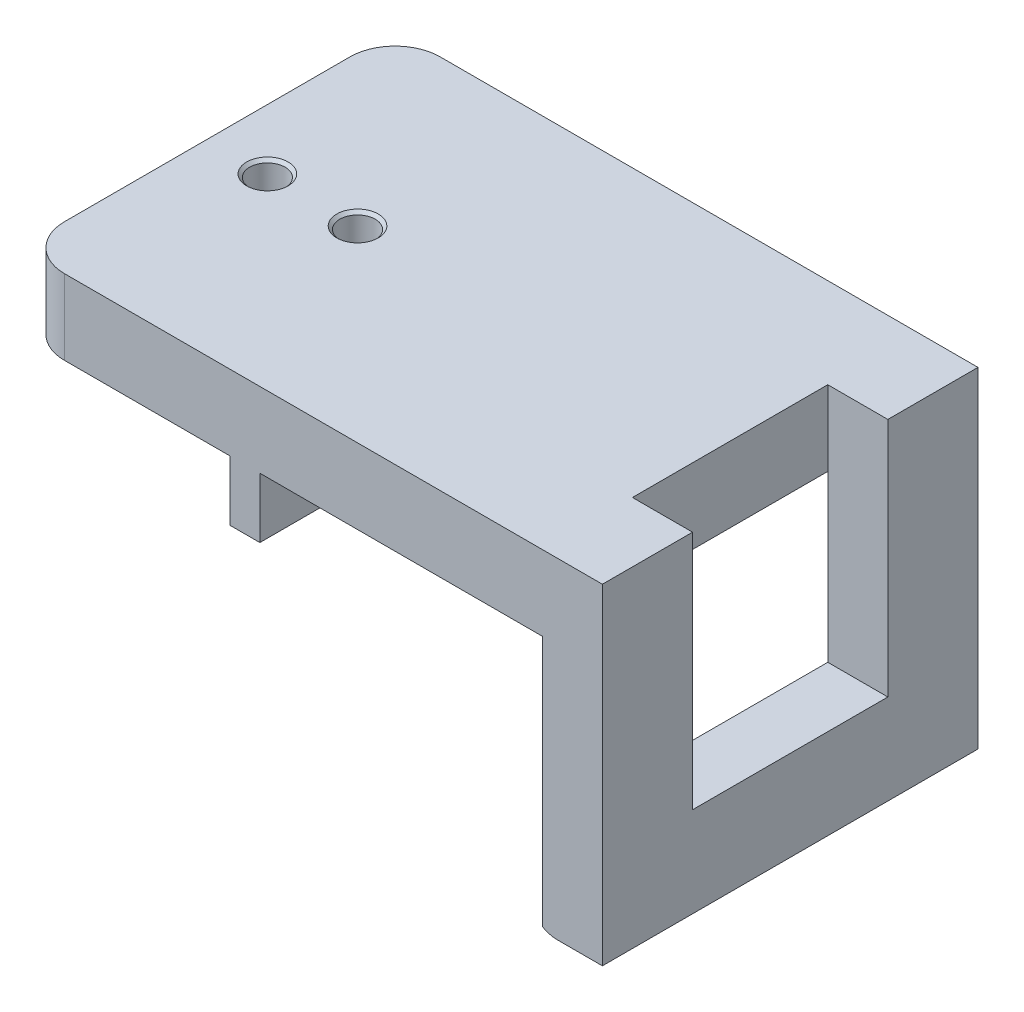
SolidWorks part; units mm, degrees
ref_plane "Front Plane" through (0, 0, 0) normal (0, 0, 1) x (1, 0, 0)
ref_plane "Top Plane" through (0, 0, 0) normal (0, 1, 0) x (1, 0, 0)
ref_plane "Right Plane" through (0, 0, 0) normal (1, 0, 0) x (0, 0, -1)
sketch "Sketch1" plane through (0, 0, 0) normal (0, 1, 0) x (1, 0, 0)
  line L1 (0, 0) -> (44.196, 0)
  line L2 (0, 0) -> (0, 31.75)
  line L3 (0, 31.75) -> (44.196, 31.75)
  line L4 (44.196, 0) -> (44.196, 31.75)
  dimension "D1" = 44.196
  dimension "D2" = 31.75
extrude "Boss-Extrude1" add sketch "Sketch1" along normal blind 6.35
sketch "Sketch3" plane through (0, 0, 0) normal (0, -1, 0) x (1, 0, 0)
  line L0 (44.196, -31.75) -> (0, -31.75) construction
  line L1 (20.32, 0) -> (17.78, 0)
  line L2 (20.32, 0) -> (20.32, -31.75)
  line L3 (20.32, -31.75) -> (17.78, -31.75)
  line L4 (17.78, 0) -> (17.78, -31.75)
  line L6 (44.196, 0) -> (44.196, -31.75) construction
  dimension "D1" = 2.54
  dimension "D2" = 23.876
extrude "Boss-Extrude3" add sketch "Sketch3" along normal blind 5.08
hole_wizard "Ø3.0mm Dowel Hole1" positions "Sketch5" profile "Sketch4" hole size "Ø3.0" standard "ISO" end condition through all
sketch "Sketch5" plane through (0, 6.35, 0) normal (0, 1, 0) x (1, 0, 0)
  line L0 (0, 0) -> (44.196, 0) construction
  line L1 (0, 31.75) -> (0, 0) construction
  point P0 (5.08, 15.875)
  point P2 (12.7, 15.875)
  dimension "D1" = 15.875
  dimension "D2" = 5.08
  dimension "D3" = 7.62
sketch "Sketch4" plane through (5.08, 6.35, -15.875) normal (1, 0, 0) x (0, 0, 1)
  line L0 (0, 0) -> (0, 11.43)
  line L1 (0, 11.43) -> (1.5, 11.43)
  line L2 (1.5, 11.43) -> (1.5, 0)
  line L5 (1.5, 0) -> (0, 0)
  line L11 (0, -6.35) -> (0, 107.95) construction
  dimension "Thru Hole Dia." = 3
  dimension "Thru Hole Depth" = 11.43
chamfer "Chamfer1" distance 0.254 angle 45 4 edges at (12.7, 6.35, -14.375) (5.08, 6.35, -14.375) (5.08, 0, -17.375) (12.7, 0, -17.375)
fillet "Fillet2" radius 3.81 2 edges at (0, 3.175, 0) (0, 3.175, -31.75)
sketch "Sketch6" plane through (44.196, 0, 0) normal (1, 0, 0) x (0, 0, -1)
  line L0 (0, 6.35) -> (0, -21.59)
  line L1 (31.75, 6.35) -> (31.75, -21.59)
  line L2 (31.75, -21.59) -> (0, -21.59)
  line L3 (0, 6.35) -> (7.62, 6.35)
  line L4 (0, 6.35) -> (31.75, 6.35) construction
  line L5 (7.62, 6.35) -> (7.62, -13.97)
  line L6 (7.62, -13.97) -> (24.13, -13.97)
  line L7 (24.13, -13.97) -> (24.13, 6.35)
  line L8 (24.13, 6.35) -> (31.75, 6.35)
  dimension "D1" = 7.62
  dimension "D2" = 7.62
  dimension "D3" = 27.94
  dimension "D4" = 7.62
extrude "Boss-Extrude4" add sketch "Sketch6" along normal blind 5.08
sketch "Sketch7" plane through (44.196, 0, 0) normal (-1, 0, 0) x (0, 0, 1)
  line L0 (0, -21.59) -> (-31.75, -21.59) construction
  line L1 (-24.13, -21.59) -> (-7.62, -21.59)
  line L2 (-24.13, -21.59) -> (-24.13, -19.05)
  line L3 (-24.13, -19.05) -> (-7.62, -19.05)
  line L4 (-7.62, -21.59) -> (-7.62, -19.05)
  line L5 (0, 0) -> (0, -21.59) construction
  line L6 (-31.75, -21.59) -> (-31.75, 0) construction
  dimension "D1" = 7.62
  dimension "D2" = 7.62
  dimension "D3" = 2.54
extrude "Boss-Extrude5" add sketch "Sketch7" along normal blind 1.27
fillet "Fillet3" radius 2.54 1 edges at (42.926, -21.59, -15.875)
